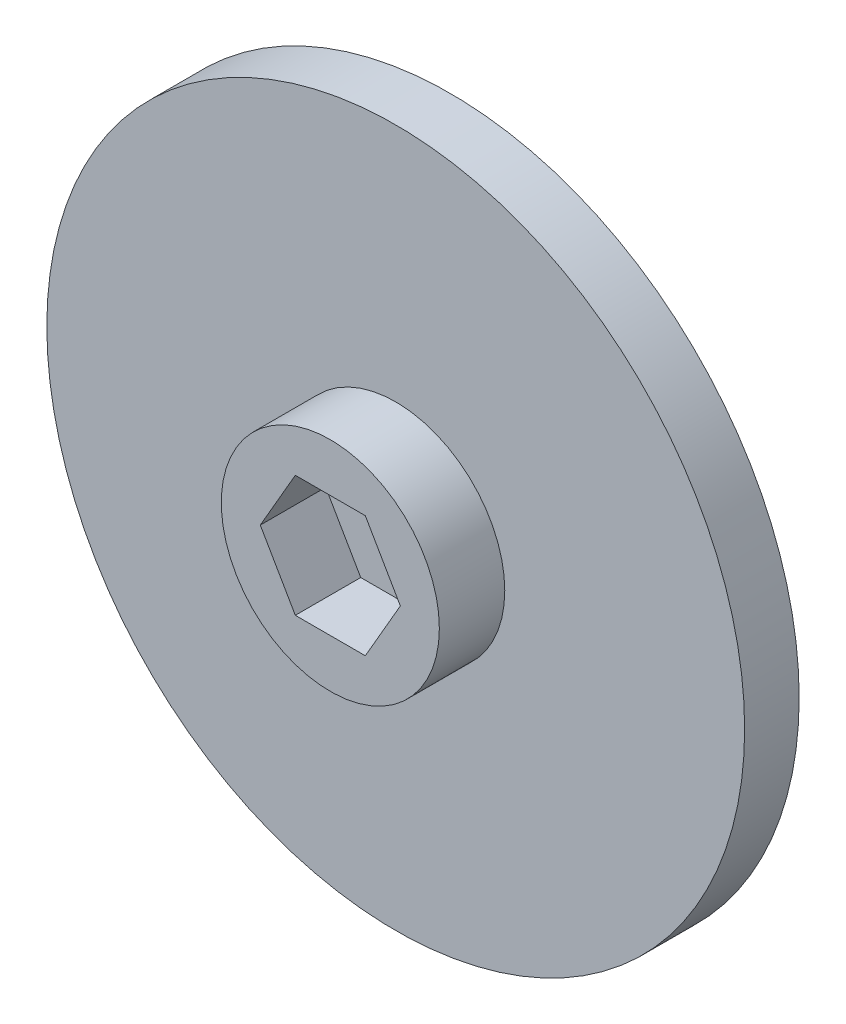
SolidWorks part; units mm, degrees
ref_plane "Front Plane" through (0, 0, 0) normal (0, 0, 1) x (1, 0, 0)
ref_plane "Top Plane" through (0, 0, 0) normal (0, 1, 0) x (1, 0, 0)
ref_plane "Right Plane" through (0, 0, 0) normal (1, 0, 0) x (0, 0, -1)
sketch "Sketch1" plane through (0, 0, 0) normal (0, 0, 1) x (1, 0, 0)
  circle A0 centre (0, 0) radius 64
  circle A1 centre (0, 0) radius 5
extrude "Boss-Extrude1" add sketch "Sketch1" along normal blind 10
sketch "Sketch2" plane through (0, 0, 10) normal (0, 0, 1) x (1, 0, 0)
  line L1 (12.8435, 0) -> (6.4217, 11.1228)
  line L2 (6.4217, 11.1228) -> (-6.4217, 11.1228)
  line L3 (-6.4217, 11.1228) -> (-12.8435, 0)
  line L4 (-12.8435, 0) -> (-6.4217, -11.1228)
  line L5 (-6.4217, -11.1228) -> (6.4217, -11.1228)
  line L6 (6.4217, -11.1228) -> (12.8435, 0)
  circle A0 centre (0, 0) radius 20
  circle A1 centre (0, 0) radius 11.1228 construction
extrude "Boss-Extrude2" add sketch "Sketch2" along normal blind 12
